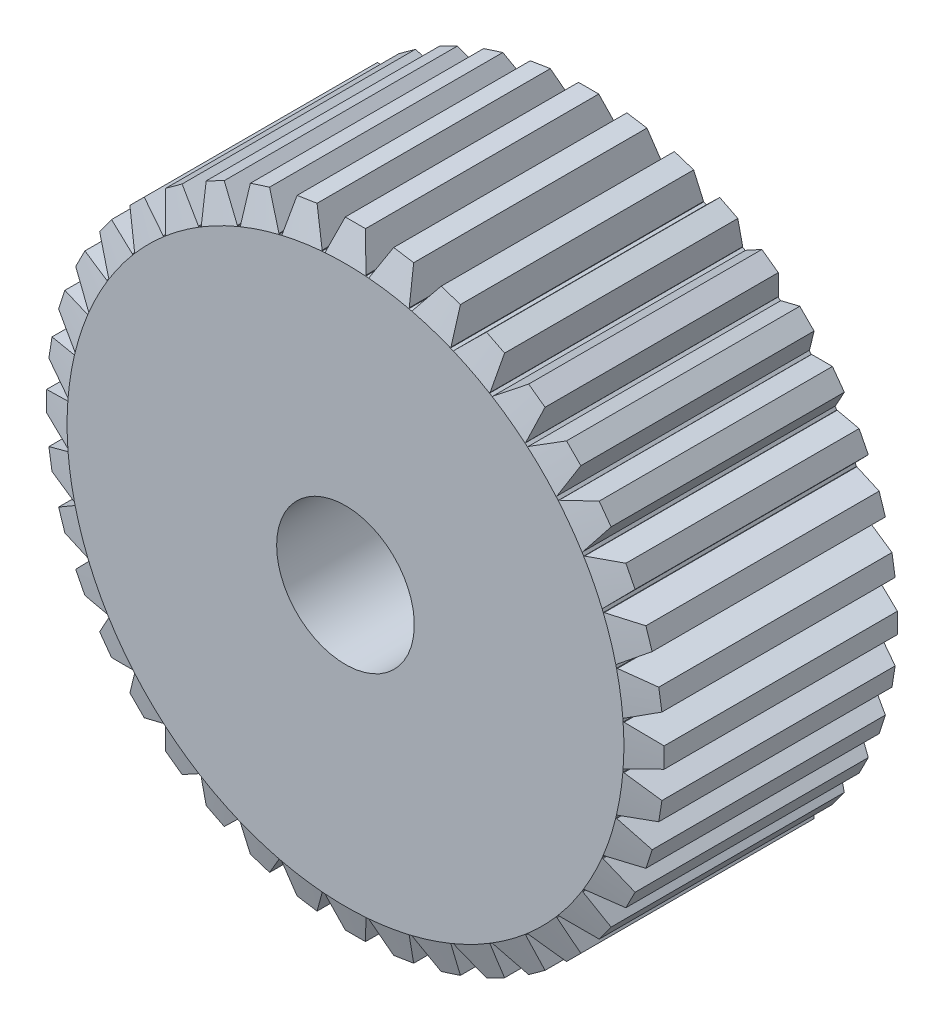
SolidWorks part; units mm, degrees
material "AISI 1020"
ref_plane "Front Plane" through (0, 0, 0) normal (0, 0, 1) x (1, 0, 0)
ref_plane "Top Plane" through (0, 0, 0) normal (0, 1, 0) x (1, 0, 0)
ref_plane "Right Plane" through (0, 0, 0) normal (1, 0, 0) x (0, 0, -1)
sketch "Sketch1" plane through (0, 0, 0) normal (0, 0, 1) x (1, 0, 0)
  circle A0 centre (0, 0) radius 6.985
  dimension "D1" = 13.97
extrude "Boss-Extrude1" add sketch "Sketch1" against normal blind 6.35
sketch "Sketch2" plane through (0, 0, 0) normal (0, 0, 1) x (1, 0, 0)
  line L2 (-0.508, 6.985) -> (-0.254, 7.747)
  line L3 (-0.254, 7.747) -> (0, 7.747)
  line L4 (0.508, 6.985) -> (0.254, 7.747)
  line L5 (0.254, 7.747) -> (0, 7.747)
  line L6 (-46.074, 6.985) -> (46.074, 6.985) construction
  line L8 (-0.508, 6.731) -> (0.508, 6.731)
  line L12 (-0.508, 6.985) -> (-0.508, 6.731)
  line L13 (0.508, 6.985) -> (0.508, 6.731)
  circle A0 centre (0, 0) radius 6.985 construction
  point P18 (0, 177.7274)
  dimension "D1" = 1.016
  dimension "D2" = 0.254
  dimension "D3" = 0.254
  dimension "D5" = 1.016
extrude "Boss-Extrude4" add sketch "Sketch2" against normal through all separate body contours L4 L5 L3 L2 L12 L8 L13
pattern_circular "CirPattern2" count 40 over 360 about axis through (0, 0, 0) along (0, 0, 1) of bodies 104
combine bodies "Combine2" bodies to combine 101 104 105 106 107 108 109 110 111 112 113 114 115 116 117 118 119 120 121 122 123 124 125 126 127 128 129 130 131 132 133 134 135 136 137 138 139 140 141 142
sketch "Sketch4" plane through (0, 0, 0) normal (1, 0, 0) x (0, 0, -1)
  line L5 (0, 0) -> (173.5338, 0) construction
  line L13 (6.096, 7.7667) -> (6.096, 8.001)
  line L14 (6.096, 8.001) -> (6.4008, 8.001)
  line L16 (6.4008, 6.985) -> (6.4008, 8.001)
  line L21 (6.096, 7.7667) -> (6.35, 6.985)
  line L22 (6.35, 6.985) -> (6.4008, 6.985)
  dimension "D1" = 0.3048
  dimension "D2" = 18
  dimension "D3" = 6.985
  dimension "D4" = 6.35
  dimension "D6" = 0.0508
ref_plane "Plane2" through (0, 0, -3.175) normal (0, 0, -1) x (-1, 0, 0)
sketch "Sketch5" plane through (0, 0, -6.35) normal (0, 0, -1) x (-1, 0, 0)
  circle A0 centre (0, 0) radius 4.318
  dimension "D1" = 8.636
extrude "Cut-Extrude1" cut sketch "Sketch5" against normal blind 1.778
sketch "Sketch6" plane through (0, 0, -4.572) normal (0, 0, -1) x (-1, 0, 0)
  circle A0 centre (0, 0) radius 2.667
  dimension "D1" = 5.334
revolve "Cut-Revolve3" cut sketch "Sketch4" angle 360 about L5
ref_plane "Plane3" through (0, 0, -3.175) normal (0, 0, 1) x (1, 0, 0)
mirror "Mirror1" about plane through (0, 0, -3.175) normal (0, 0, 1) of "Cut-Revolve3"
hole_wizard "#8-32 Tapped Hole1" positions "Sketch9" profile "Sketch10" tap size "#8-32" standard "ANSI Inch" end condition through all
sketch "Sketch9" plane through (0, 0, -4.572) normal (0, 0, -1) x (-1, 0, 0)
  point P0 (0, 0)
sketch "Sketch10" plane through (0, 0, -4.572) normal (1, 0, 0) x (0, 1, 0)
  line L0 (0, 0) -> (0, 4.572)
  line L1 (0, 4.572) -> (1.7272, 4.572)
  line L2 (1.7272, 4.572) -> (1.7272, 0)
  line L5 (1.7272, 0) -> (0, 0)
  line L11 (0, -6.35) -> (0, 107.95) construction
  dimension "Thru Tap Drill Dia." = 3.4544
  dimension "Thru Tap Drill Depth" = 4.572
cosmetic thread "Hole Thread1" parameters "D2"=4.1656
